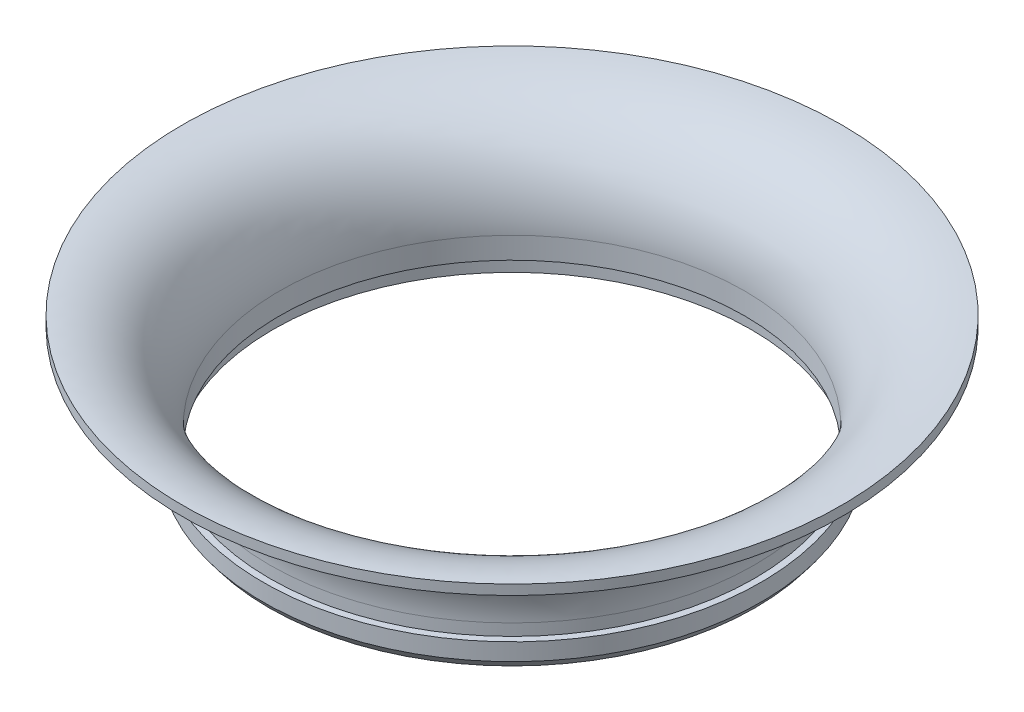
SolidWorks part; units mm, degrees
ref_plane "Front Plane" through (0, 0, 0) normal (0, 0, 1) x (1, 0, 0)
ref_plane "Top Plane" through (0, 0, 0) normal (0, 1, 0) x (1, 0, 0)
ref_plane "Right Plane" through (0, 0, 0) normal (1, 0, 0) x (0, 0, -1)
sketch "Sketch1" plane through (0, 0, 0) normal (0, 0, 1) x (1, 0, 0)
  line L0 (0, 0) -> (30.4865, 0) construction
  line L1 (0, 0) -> (0, 36.8) construction
  line L2 (0, 0) -> (-49.9, 0) construction
  line L3 (-49.9, 0) -> (-49.9, 28.4324) construction
  line L4 (-36.8, 0) -> (-36.2, 0)
  line L5 (-36.2, 0) -> (-36.2, 2.3)
  line L6 (-36.2, 2.3) -> (-35.2, 2.3)
  line L7 (-35.2, 2.3) -> (-35.2, 5.5676)
  line L8 (-35.2, 13.3529) -> (-35.2, -2.2177) construction
  line L9 (-58.3249, 20) -> (-41.4751, 20) construction
  line L10 (-37.7, 1.2) -> (-37.7, 1.2)
  line L11 (-37.7, 1.2) -> (-37.7, 3.8)
  line L12 (-37.7, 3.8) -> (-36.7, 3.8)
  line L13 (-36.7, 3.8) -> (-36.7, 5.5676)
  line L14 (-36.8, 0) -> (-37.7, 1.2)
  line L15 (-49.9, 20) -> (-49.9, 18.5)
  spline S0 degree 3 poles (-35.2, 5.5676) (-35.2, 12.0553) (-39.3688, 20) (-49.9, 20) knots 0 0 0 0 1 1 1 1
  spline S1 degree 1 poles (-36.7, 5.5676) (-49.9, 18.5) knots 0 0 1 1 construction
  spline S2 degree 3 poles (-36.7, 5.5676) (-36.7, 6.3183) (-36.8177, 7.7993) (-37.3724, 10.1008) (-38.3216, 12.2955) (-39.6771, 14.2976) (-41.4552, 16.0127) (-43.3188, 17.1398) (-45.0697, 17.8172) (-46.5208, 18.1998) (-47.8555, 18.402) (-48.9938, 18.4856) (-49.601, 18.5) (-49.9, 18.5) knots 0 0 0 0 0.125 0.25 0.375 0.5 0.625 0.75 0.8125 0.875 0.9375 0.96875 1 1 1 1
  dimension "D1" = 20
  dimension "D2" = 0.6
  dimension "D3" = 1.6
  dimension "D4" = 49.9
  dimension "D5" = 1.5
  dimension "D6" = 36.8
  dimension "D7" = 2.3
revolve "Revolve1" add sketch "Sketch1" angle 360 about L1
